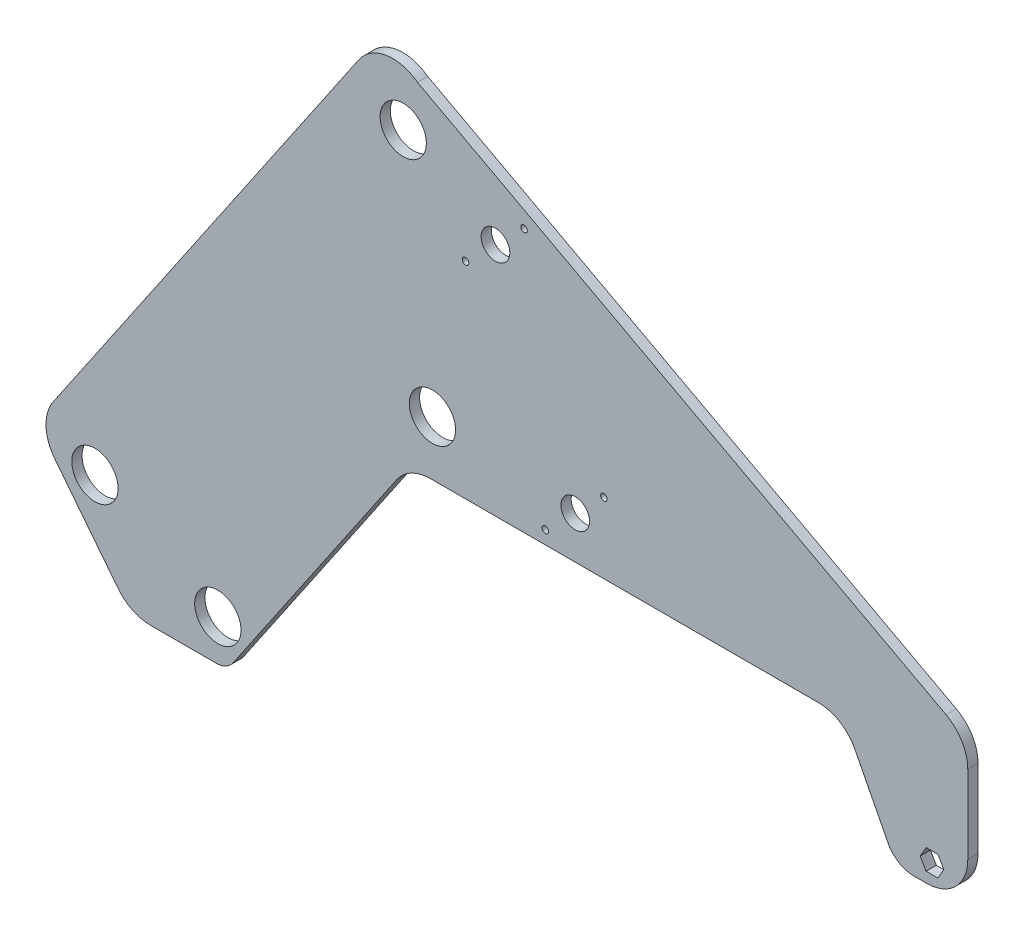
SolidWorks part; units mm, degrees
other "Markup1"
sketch "Sketch1" plane through (-441.7893, 331.8239, 6.35) normal (-0.0431, 0.0102, 0.999) x (0.9985, 0.0354, 0.0427)
sketch "Sketch2" plane through (-413.6701, 343.933, 6.35) normal (-0.0431, 0.0102, 0.999) x (0.9985, 0.0354, 0.0427)
sketch "Sketch3" plane through (-436.3774, 318.5567, 6.35) normal (-0.0431, 0.0102, 0.999) x (0.9985, 0.0354, 0.0427)
sketch "Sketch5" plane through (-436.3774, 318.5567, 6.35) normal (-0.0431, 0.0102, 0.999) x (0.9985, 0.0354, 0.0427)
sketch "Sketch7" plane through (-430.3226, 318.5567, 6.35) normal (-0.0431, 0.0102, 0.999) x (0.9985, 0.0354, 0.0427)
sketch "Sketch9" plane through (-430.3226, 318.5567, 6.35) normal (-0.0431, 0.0102, 0.999) x (0.9985, 0.0354, 0.0427)
sketch "Sketch11" plane through (-430.3226, 318.5567, 6.35) normal (-0.0431, 0.0102, 0.999) x (0.9985, 0.0354, 0.0427)
other "Markup2"
sketch "Sketch4" plane through (102.4721, 318.5567, 6.35) normal (0.9364, 0.1073, 0.3342) x (0.3416, -0.0598, -0.9379)
sketch "Sketch6" plane through (102.4721, 318.5567, 6.35) normal (0.9364, 0.1073, 0.3342) x (0.3416, -0.0598, -0.9379)
sketch "Sketch8" plane through (141.2086, 318.5567, 6.35) normal (0.9364, 0.1073, 0.3342) x (0.3416, -0.0598, -0.9379)
sketch "Sketch10" plane through (141.2086, 318.5567, 6.35) normal (0.9364, 0.1073, 0.3342) x (0.3416, -0.0598, -0.9379)
sketch "Sketch12" plane through (141.2086, 318.5567, 6.35) normal (0.9364, 0.1073, 0.3342) x (0.3416, -0.0598, -0.9379)
material "Lexan"
ref_plane "Front Plane" through (0, 0, 0) normal (0, 0, 1) x (1, 0, 0)
ref_plane "Top Plane" through (0, 0, 0) normal (0, 1, 0) x (1, 0, 0)
ref_plane "Right Plane" through (0, 0, 0) normal (1, 0, 0) x (0, 0, -1)
sketch "Model" plane through (0, 0, 0) normal (0, 0, 1) x (1, 0, 0)
  line L1 (-191.9011, 104.6502) -> (-112.96, 104.6502)
  line L3 (-314.2383, -55.3595) -> (-212.8994, 93.5413)
  line L4 (-236.3032, 307.4477) -> (-425.9209, 28.8361)
  line L5 (-424.8981, -1.1437) -> (-385.5815, -51.2028)
  line L13 (126.3831, 53.8502) -> (122.717, 60.2002)
  line L14 (122.717, 60.2002) -> (115.3846, 60.2002)
  line L15 (115.3846, 60.2002) -> (111.7185, 53.8502)
  line L16 (111.7185, 53.8502) -> (115.3846, 47.5002)
  line L17 (115.3846, 47.5002) -> (122.717, 47.5002)
  line L18 (122.717, 47.5002) -> (126.3831, 53.8502)
  line L19 (-365.606, -60.914) -> (-324.7375, -60.914)
  line L20 (-871.0211, -88.854) -> (370.1019, -88.854) construction
  line L22 (141.2086, 66.5502) -> (141.2086, 78.8846)
  line L27 (107.6196, 41.1502) -> (115.8086, 41.1502)
  line L28 (-399.9752, 2.586) -> (-323.7752, -35.514) construction
  line L29 (-323.7752, -35.514) -> (-190.7071, 138.5169) construction
  line L30 (-190.7071, 138.5169) -> (-208.8329, 283.4378) construction
  line L31 (-208.8329, 283.4378) -> (-399.9752, 2.586) construction
  line L32 (91.8004, 50.8135) -> (71.26, 90.8456)
  line L33 (48.6612, 104.6502) -> (-11.3966, 104.6502)
  line L34 (141.2086, 78.8846) -> (141.2086, 115.3033)
  line L35 (127.8091, 137.6897) -> (-86.3327, 252.4836)
  line L36 (-112.96, 104.6502) -> (-68.51, 104.6502)
  line L40 (-68.51, 104.6502) -> (-2.1388, 104.6502)
  line L41 (-122.3008, 271.7648) -> (-199.9496, 313.3896)
  line L42 (-122.3008, 271.7648) -> (-86.3327, 252.4836)
  arc A3 (121.2475, 59.8082) -> (121.352, 60.2002) centre (96.7586, 66.5502) ccw
  circle A9 centre (-323.7752, -35.514) radius 14.351
  circle A10 centre (-399.9752, 2.586) radius 14.351
  circle A12 centre (-190.7071, 138.5169) radius 14.351
  arc A15 (107.6196, 41.1502) -> (91.8004, 50.8135) centre (107.6196, 58.9302) cw
  arc A21 (-191.9011, 104.6502) -> (-212.8994, 93.5413) centre (-191.9011, 79.2502) ccw
  circle A22 centre (-208.8329, 283.4378) radius 14.351
  circle A24 centre (119.0508, 53.8502) radius 6.35 construction
  arc A31 (-324.7375, -60.914) -> (-314.2383, -55.3595) centre (-324.7375, -48.214) ccw
  arc A40 (114.7422, 48.6129) -> (115.0458, 48.9225) centre (96.7586, 66.5502) ccw
  arc A43 (115.8086, 41.1502) -> (141.2086, 66.5502) centre (115.8086, 66.5502) ccw
  arc A44 (-236.3032, 307.4477) -> (-199.9496, 313.3896) centre (-215.305, 293.1567) cw
  arc A45 (-365.606, -60.914) -> (-385.5815, -51.2028) centre (-365.606, -35.514) cw
  arc A46 (71.26, 90.8456) -> (48.6612, 104.6502) centre (48.6612, 79.2502) ccw
  arc A47 (141.2086, 115.3033) -> (127.8091, 137.6897) centre (115.8086, 115.3033) ccw
  arc A48 (-424.8981, -1.1437) -> (-425.9209, 28.8361) centre (-404.9226, 14.5451) cw
  ellipse E0 centre (-551.1692, 173.9527) end of major axis (-591.2054, 216.0961) minor radius 17.278
  point P31 (-177.5612, 330.9695)
  point P34 (100.2935, -12.8222)
  point P43 (-377.9543, -60.914)
  point P55 (96.7586, 41.1502)
  point P59 (174.831, 53.8502)
  point P60 (-205.3388, 104.6502)
  point P64 (-436.3774, 13.472)
  dimension "D3" = 38.1
  dimension "D4" = 104.6502
  dimension "D5" = 76.2
  dimension "D6" = 44.45
  dimension "D7" = 12.7
  dimension "D8" = 28.702
  dimension "D11" = 139.7
  dimension "D12" = 27.94
  dimension "D21" = 124.238
  dimension "D13" = 12.7
  dimension "D16" = 355.6
  dimension "D23" = 25.4
  dimension "D24" = 25.4
  dimension "D26" = 25.4
  dimension "D14" = 406.4
  dimension "D20" = 254
  dimension "D29" = 25.4
  dimension "D31" = 25.4
  dimension "D25" = 88.9
  dimension "D30" = 17.78
  dimension "D32" = 25.4
  dimension "D33" = 25.4
  dimension "D9" = 19.05
  dimension "D10" = 146.05
  dimension "D15" = 33.8667
  dimension "D17" = 339.725
  dimension "D18" = 219.075
  dimension "D19" = 50.8
  dimension "D22" = 25.4
  dimension "D27" = 53.2168
  dimension "D28" = 12.7
extrude "Boss-Extrude1" add sketch "Model" along normal blind 6.35 contours L5 L3 L1 L4 A22 A9 A10 A12 region at (-206.9871, 107.7659, 0)
sketch "Sketch13" plane through (0, 0, 6.35) normal (0, 0, 1) x (1, 0, 0)
  line L0 (-133.9094, 267.8191) -> (-133.9094, 265.7871)
  line L1 (-170.1879, 232.2591) -> (-170.1879, 230.2271)
  line L2 (-135.9414, 267.8191) -> (-172.2199, 267.8191)
  line L3 (-172.2199, 267.8191) -> (-172.2199, 232.2591)
  line L4 (-84.4349, 148.3622) -> (-84.4349, 146.3302)
  line L5 (-120.7134, 112.8022) -> (-120.7134, 110.7702)
  line L6 (-86.4669, 148.3622) -> (-122.7454, 148.3622)
  line L7 (-122.7454, 148.3622) -> (-122.7454, 112.8022)
  line L8 (-133.9094, 265.7871) -> (-133.9094, 243.6891)
  line L9 (-133.9094, 243.6891) -> (-155.4994, 243.6891)
  line L10 (-84.4349, 146.3302) -> (-84.4349, 124.2322)
  line L11 (-155.4994, 243.6891) -> (-147.7524, 243.6891)
  line L12 (-147.7524, 243.6891) -> (-143.8789, 250.3982)
  line L13 (-143.8789, 250.3982) -> (-147.7524, 257.1073)
  line L14 (-147.7524, 257.1073) -> (-155.4994, 257.1073)
  line L15 (-155.4994, 257.1073) -> (-159.3729, 250.3982)
  line L16 (-159.3729, 250.3982) -> (-155.4994, 243.6891)
  line L17 (-84.4349, 124.2322) -> (-106.0249, 124.2322)
  line L18 (-106.0249, 124.2322) -> (-96.4929, 124.2322)
  line L24 (-107.9617, 127.5868) -> (-96.3412, 134.2959)
  line L26 (-106.0249, 124.2322) -> (-98.2779, 124.2322)
  line L27 (-98.2779, 124.2322) -> (-94.4044, 130.9413)
  line L28 (-94.4044, 130.9413) -> (-98.2779, 137.6504)
  line L29 (-98.2779, 137.6504) -> (-106.0249, 137.6504)
  line L30 (-106.0249, 137.6504) -> (-109.8984, 130.9413)
  line L31 (-109.8984, 130.9413) -> (-106.0249, 124.2322)
  circle A0 centre (-170.1879, 232.2591) radius 2.032
  circle A1 centre (-133.9094, 267.8191) radius 2.032
  circle A6 centre (-151.6259, 250.3982) radius 6.7091 construction
  circle A7 centre (-120.7134, 112.8022) radius 2.032
  circle A8 centre (-84.4349, 148.3622) radius 2.032
  circle A9 centre (-151.6259, 250.3982) radius 8.89
  circle A10 centre (-102.1514, 130.9413) radius 8.89
  dimension "D1" = 4.064
  dimension "D2" = 4.064
  dimension "D3" = 22.098
  dimension "D4" = 21.59
  dimension "D8" = 4.064
  dimension "D9" = 4.064
  dimension "D16" = 17.78
  dimension "D17" = 17.78
  dimension "D5" = 50.8
  dimension "D6" = 90
  dimension "D7" = 35.56
  dimension "D10" = 50.8
  dimension "D11" = 90
  dimension "D12" = 35.56
  dimension "D13" = 15.494
  dimension "D14" = 22.098
  dimension "D15" = 21.59
extrude "Cut-Extrude4" cut sketch "Sketch13" against normal through all contours A9 L9 L16 L15 L14 L13 L12 | L15 L16 L9 L12 L13 L14 | A0 | A1 | L30 L31 L24 L28 L29 | L24 L31 L18 L27 L28 | A8 | A7 | A10 L18 L31 L30 L29 L28 L27 region at (-170.1879, 234.2337, 6.35) region at (-151.6259, 250.3982, 6.35) region at (-159.4867, 253.9804, 6.35) region at (-133.9094, 269.7937, 6.35) region at (-120.7134, 114.7767, 6.35) region at (-100.6451, 128.3322, 6.35) region at (-110.0123, 134.5235, 6.35) region at (-84.4349, 150.3367, 6.35) region at (-103.6578, 133.5504, 6.35)
